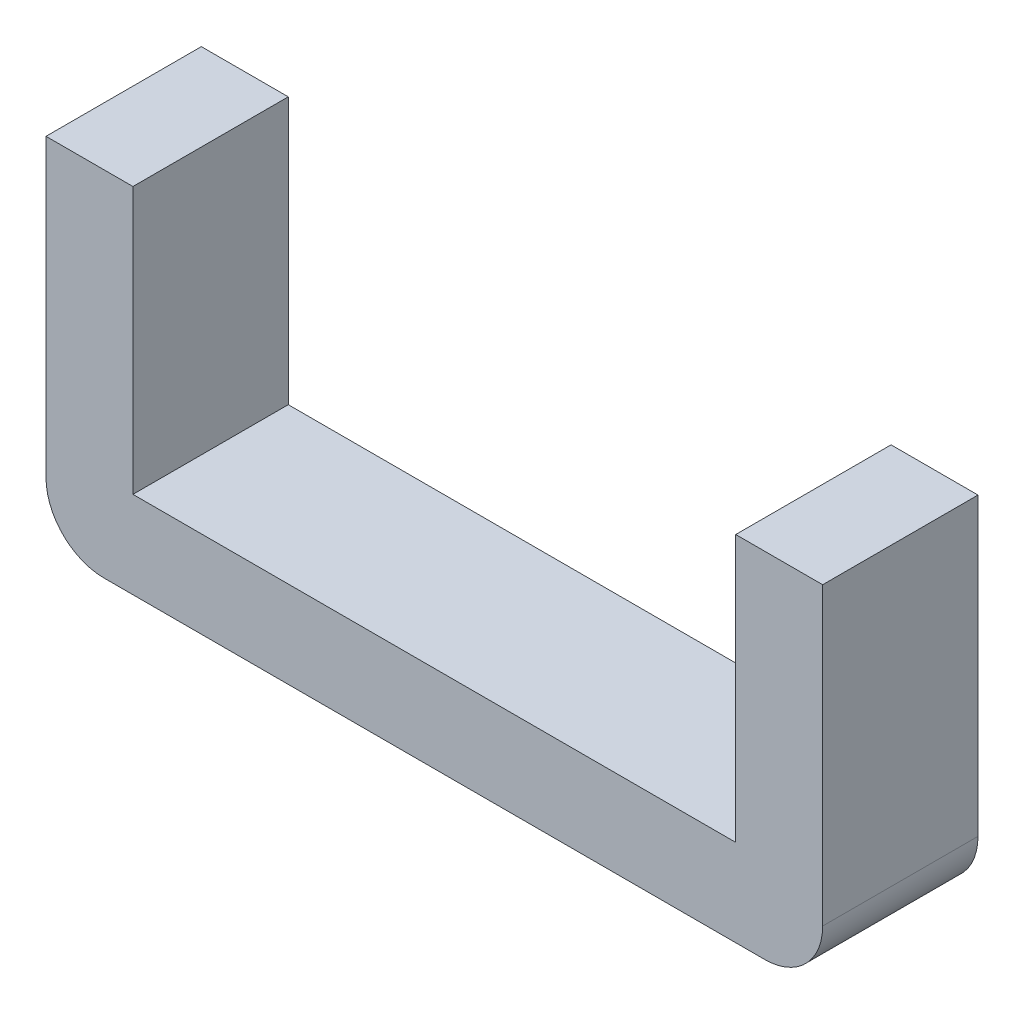
SolidWorks part; units mm, degrees
ref_plane "Front Plane" through (0, 0, 0) normal (0, 0, 1) x (1, 0, 0)
ref_plane "Top Plane" through (0, 0, 0) normal (0, 1, 0) x (1, 0, 0)
ref_plane "Right Plane" through (0, 0, 0) normal (1, 0, 0) x (0, 0, -1)
sketch "Sketch1" plane through (0, 0, 0) normal (0, 1, 0) x (1, 0, 0)
  line L0 (-26, -24.8946) -> (26, -24.8946)
  line L2 (26, -11.4946) -> (26, -24.8946)
  line L4 (-26, -11.4946) -> (-26, -24.8946)
  line L5 (-26, -11.4946) -> (26, -11.4946)
  line L6 (12.1, -24.8946) -> (0.7, -24.8946) construction
  line L7 (-26, -11.4946) -> (-31, -11.4946)
  line L8 (-26, -11.4946) -> (-26, -24.8946)
  line L9 (-26, -24.8946) -> (-31, -24.8946)
  line L10 (-31, -11.4946) -> (-31, -24.8946)
  line L11 (26, -11.4946) -> (31, -11.4946)
  line L12 (26, -11.4946) -> (26, -24.8946)
  line L13 (26, -24.8946) -> (31, -24.8946)
  line L14 (31, -11.4946) -> (31, -24.8946)
  line L15 (-12.7, -11.4946) -> (-1.3, -11.4946) construction
  point P0 (0, 0)
extrude "Boss-Extrude3" add sketch "Sketch1" along normal blind 7.5 contours L4 L0 L2 region at (0, 0, 18.1946)
sketch "Sketch2" plane through (0, 0, 0) normal (0, 1, 0) x (1, 0, 0)
  line L0 (-26, -11.4946) -> (-26, -24.8946)
  line L1 (-33.5, -11.4946) -> (-26, -11.4946)
  line L2 (-26, -11.4946) -> (-26, -24.8946)
  line L3 (-26, -24.8946) -> (-33.5, -24.8946)
  line L4 (-33.5, -11.4946) -> (-33.5, -24.8946)
  line L5 (-26, -11.4946) -> (26, -11.4946) construction
  line L7 (-26, -24.8946) -> (26, -24.8946) construction
  line L8 (0, -24.8946) -> (0, -11.4946) construction
  line L9 (33.5, -11.4946) -> (33.5, -24.8946)
  line L10 (26, -24.8946) -> (33.5, -24.8946)
  line L11 (26, -11.4946) -> (26, -24.8946)
  line L12 (33.5, -11.4946) -> (26, -11.4946)
  line L13 (26, -11.4946) -> (26, -24.8946)
  line L14 (-26, -11.4946) -> (-26, -24.8946) construction
  dimension "D1" = 7.5
extrude "Boss-Extrude4" add sketch "Sketch2" along normal up to surface (30.5 mm away) contours L1 L4 L3 L0 | L9 L12 L11 L10 region at (-29.75, 0, 18.1946) region at (29.75, 0, 18.1946)
fillet "Fillet1" radius 5 2 edges at (33.5, 0, 18.1946) (-33.5, 0, 18.1946)
